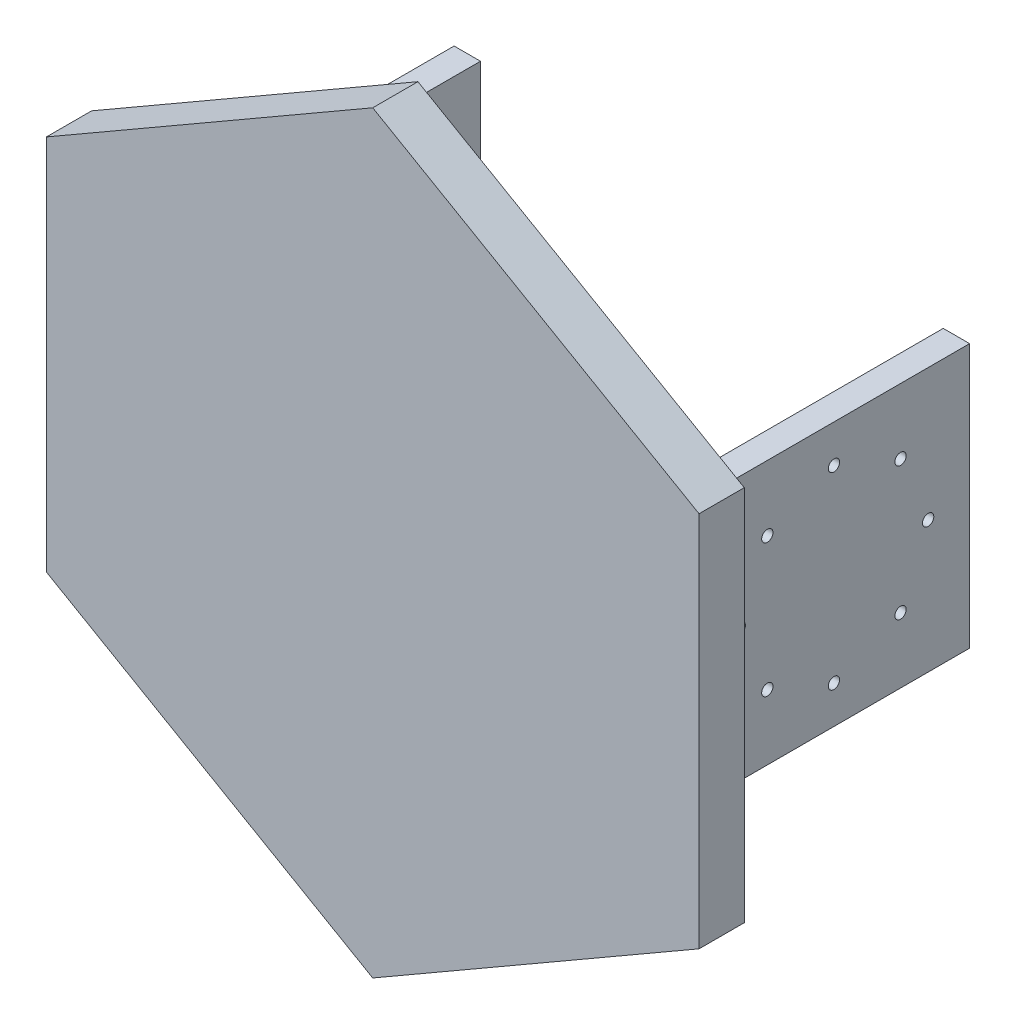
SolidWorks part; units mm, degrees
material "PPE"
ref_plane "Front Plane" through (0, 0, 0) normal (0, 0, 1) x (1, 0, 0)
ref_plane "Top Plane" through (0, 0, 0) normal (0, 1, 0) x (1, 0, 0)
ref_plane "Right Plane" through (0, 0, 0) normal (1, 0, 0) x (0, 0, -1)
sketch "Sketch1" plane through (0, 0, 0) normal (0, 1, 0) x (1, 0, 0)
  line L0 (-29.2, 0) -> (29.2, 0)
  line L1 (34.2, 5) -> (34.2, 45)
  line L2 (34.2, 45) -> (30.7, 45)
  line L3 (-30.7, 45) -> (-30.7, 10)
  line L5 (-25.7, 5) -> (25.7, 5)
  line L6 (-30.7, 45) -> (-34.2, 45)
  line L7 (-34.2, 45) -> (-34.2, 5)
  line L8 (30.7, 10) -> (30.7, 45)
  arc A0 (25.7, 5) -> (30.7, 10) centre (25.7, 10) ccw
  arc A1 (29.2, 0) -> (34.2, 5) centre (29.2, 5) ccw
  arc A2 (-30.7, 10) -> (-25.7, 5) centre (-25.7, 10) ccw
  arc A3 (-34.2, 5) -> (-29.2, 0) centre (-29.2, 5) ccw
  point P0 (0, 0)
  point P13 (30.7, 5)
  point P16 (34.2, 0)
  point P19 (-30.7, 5)
  point P22 (-34.2, 0)
  dimension "D5" = 5
  dimension "D1" = 68.4
  dimension "D2" = 61.4
  dimension "D3" = 40
  dimension "D4" = 45
extrude "Boss-Extrude1" add sketch "Sketch1" along normal mid plane 35
sketch "Sketch2" plane through (-34.2, 0, 0) normal (-1, 0, 0) x (0, 0, 1)
  line L1 (-45, 17.5) -> (-45, -17.5) construction
  line L2 (-39.5, 0) -> (-14.5, 0) construction
  line L6 (-27, 12.5) -> (-27, -12.5) construction
  circle A0 centre (-27, 0) radius 15
  circle A1 centre (-27, 0) radius 12.5
  circle A2 centre (-27, 12.5) radius 0.75
  circle A3 centre (-18.1612, 8.8388) radius 0.75
  circle A4 centre (-27, 0) radius 12.5
  circle A5 centre (-14.5, 0) radius 0.75
  circle A6 centre (-27, 0) radius 12.5
  circle A7 centre (-18.1612, -8.8388) radius 0.75
  circle A8 centre (-27, 0) radius 12.5
  circle A9 centre (-27, -12.5) radius 0.75
  circle A10 centre (-27, 0) radius 12.5
  circle A11 centre (-35.8388, -8.8388) radius 0.75
  circle A12 centre (-27, 0) radius 12.5
  circle A13 centre (-39.5, 0) radius 0.75
  circle A14 centre (-27, 0) radius 12.5
  circle A15 centre (-35.8388, 8.8388) radius 0.75
  circle A16 centre (-27, 0) radius 12.5
  circle A17 centre (-27, -12.5) radius 0.75 [skipped]
  point P8 (-45, 0)
  point P44 (-27, 0)
  dimension "D1" = 30
  dimension "D2" = 25
  dimension "D3" = 1.5
  dimension "D4" = 8
  dimension "D5" = 18
  dimension "D6" = 1.5
extrude "Cut-Extrude1" cut sketch "Sketch2" against normal up to surface (68.4 mm away) contours A1 A2 | A14 A15 | A14 A15 | A2 | A13 | A11 | A7 | A5 | A3 region at (-34.2, 12.8142, -27) region at (-34.2, 8.6109, -35.6109) region at (-34.2, 9.061, -36.061) up to face at (34.2, 0, -25)
extrude "Cut-Extrude2" cut sketch "Sketch2<3>" against normal through all contours A9
sketch "Sketch2<3>" plane through (-34.2, 0, 0) normal (-1, 0, 0) x (0, 0, 1) same geometry as "Sketch2"
sketch "Sketch3" plane through (0, 0, 0) normal (0, 0, 1) x (1, 0, 0)
  line L0 (-29.2, 17.5) -> (-29.2, -17.5) construction
  line L1 (-41.3, -17.5) -> (41.3, -17.5)
  line L2 (-41.3, -17.5) -> (-41.3, 17.5)
  line L3 (-41.3, 17.5) -> (41.3, 17.5)
  line L4 (41.3, -17.5) -> (41.3, 17.5)
  point P7 (0, 17.5)
  point P8 (-41.3, -6.7837)
  dimension "D1" = 82.6
  dimension "D2" = 17.5
extrude "Boss-Extrude2" add sketch "Sketch3" against normal blind 6
sketch "Sketch5" plane through (0, 0, 0) normal (0, 0, 1) x (1, 0, 0)
  line L1 (43.3013, 25) -> (0, 50)
  line L2 (0, 50) -> (-43.3013, 25)
  line L3 (-43.3013, 25) -> (-43.3013, -25)
  line L4 (-43.3013, -25) -> (0, -50)
  line L5 (0, -50) -> (43.3013, -25)
  line L6 (43.3013, -25) -> (43.3013, 25)
  circle A0 centre (0, 0) radius 43.3013 construction
  point P1 (0, 0)
  point P10 (0, 0)
  point P11 (0, 0)
  dimension "D1" = 50
extrude "Boss-Extrude3" add sketch "Sketch5" against normal blind 6
